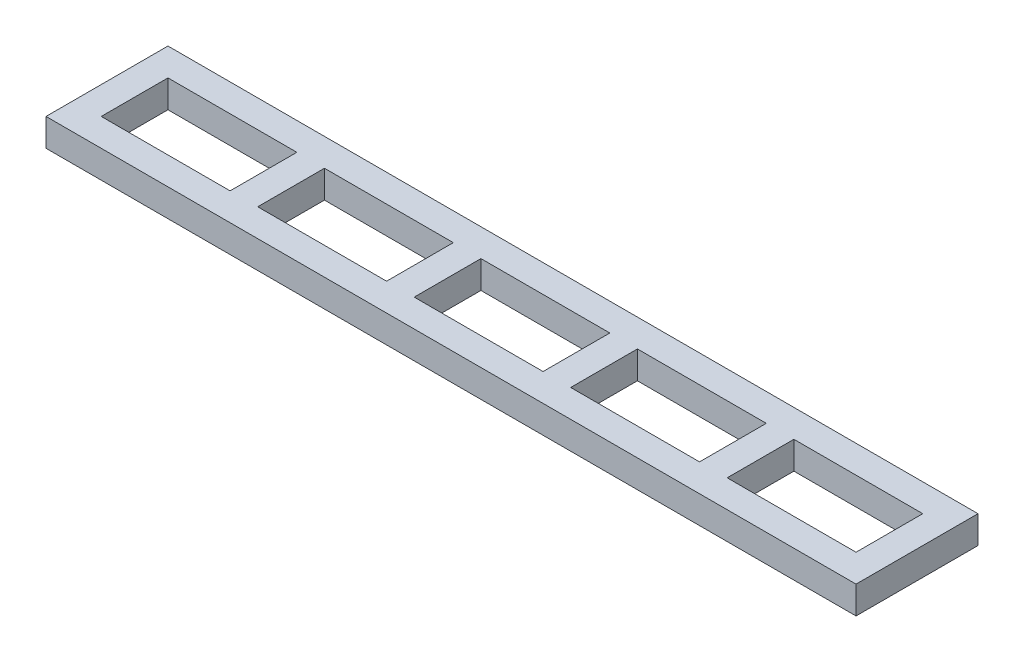
SolidWorks part; units mm, degrees
material "Pine"
ref_plane "Front Plane" through (0, 0, 0) normal (0, 0, 1) x (1, 0, 0)
ref_plane "Top Plane" through (0, 0, 0) normal (0, 1, 0) x (1, 0, 0)
ref_plane "Right Plane" through (0, 0, 0) normal (1, 0, 0) x (0, 0, -1)
sketch "Sketch1" plane through (0, 0, 0) normal (1, 0, 0) x (0, 0, -1)
  line L1 (-42.0688, -9.525) -> (42.0688, -9.525)
  line L2 (-42.0688, -9.525) -> (-42.0688, 9.525)
  line L3 (-42.0688, 9.525) -> (42.0688, 9.525)
  line L4 (42.0688, -9.525) -> (42.0688, 9.525)
  line L5 (-42.0688, -9.525) -> (42.0688, 9.525) construction
  line L6 (-42.0688, 9.525) -> (42.0688, -9.525) construction
  point P0 (0, 0)
  dimension "D1" = 84.1375
  dimension "D2" = 19.05
extrude "Boss-Extrude1" add sketch "Sketch1" along normal mid plane 558.8
sketch "Sketch2" plane through (0, 9.525, 0) normal (0, 1, 0) x (1, 0, 0)
  line L10 (171.45, 0) -> (152.4, 0) construction
  line L11 (-260.35, 23.0188) -> (-171.45, 23.0188)
  line L12 (-260.35, 23.0188) -> (-260.35, -23.0188)
  line L13 (-260.35, -23.0188) -> (-171.45, -23.0188)
  line L14 (260.35, 23.0188) -> (260.35, -23.0188)
  line L15 (260.35, 0) -> (279.4, 0) construction
  line L16 (279.4, 42.0688) -> (279.4, -42.0688) construction
  line L17 (-260.35, 0) -> (-279.4, 0) construction
  line L18 (-279.4, 42.0688) -> (-279.4, -42.0688) construction
  line L19 (215.9, 23.0188) -> (215.9, 42.0688) construction
  line L20 (279.4, 42.0688) -> (-279.4, 42.0688) construction
  line L22 (-171.45, 23.0188) -> (-171.45, -23.0188)
  line L23 (-152.4, 23.0188) -> (-63.5, 23.0188)
  line L24 (-152.4, 23.0188) -> (-152.4, -23.0188)
  line L25 (-152.4, -23.0188) -> (-63.5, -23.0188)
  line L26 (-63.5, 23.0188) -> (-63.5, -23.0188)
  line L27 (-44.45, 23.0188) -> (44.45, 23.0188)
  line L28 (-44.45, 23.0188) -> (-44.45, -23.0188)
  line L29 (-44.45, -23.0188) -> (44.45, -23.0188)
  line L30 (44.45, 23.0188) -> (44.45, -23.0188)
  line L31 (63.5, 23.0188) -> (152.4, 23.0188)
  line L32 (63.5, 23.0188) -> (63.5, -23.0188)
  line L33 (63.5, -23.0188) -> (152.4, -23.0188)
  line L34 (152.4, 23.0188) -> (152.4, -23.0188)
  line L35 (260.35, 23.0188) -> (171.45, 23.0188)
  line L37 (260.35, -23.0188) -> (171.45, -23.0188)
  line L38 (171.45, 23.0188) -> (171.45, -23.0188)
  line L40 (63.5, 0) -> (44.45, 0) construction
  line L42 (-44.45, 0) -> (-63.5, 0) construction
  line L44 (-152.4, 0) -> (-171.45, 0) construction
  dimension "D2" = 19.05
extrude "Cut-Extrude1" cut sketch "Sketch2" against normal through all
